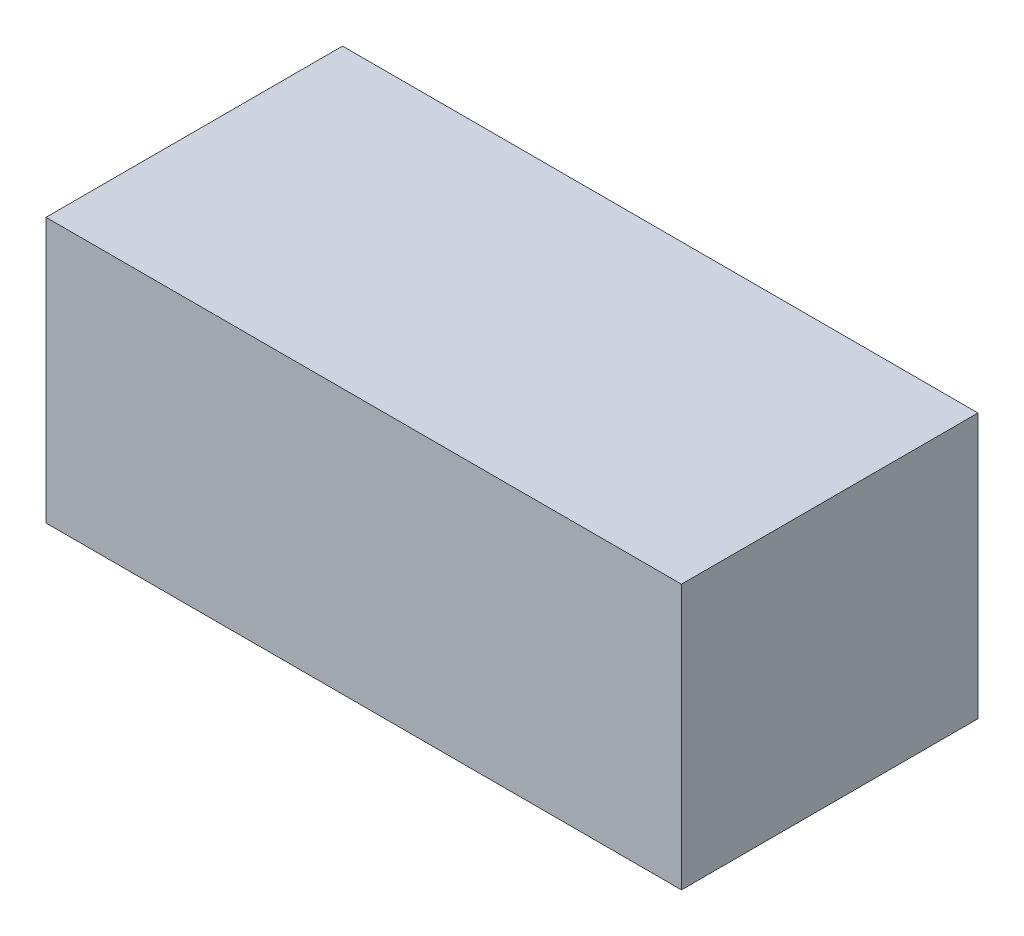
SolidWorks part; units mm, degrees
ref_plane "Front Plane" through (0, 0, 0) normal (0, 0, 1) x (1, 0, 0)
ref_plane "Top Plane" through (0, 0, 0) normal (0, 1, 0) x (1, 0, 0)
ref_plane "Right Plane" through (0, 0, 0) normal (1, 0, 0) x (0, 0, -1)
sketch "Sketch2" plane through (0, 0, 0) normal (0, 1, 0) x (1, 0, 0)
  line L1 (-30, 14) -> (30, 14)
  line L2 (-30, 14) -> (-30, -14)
  line L3 (-30, -14) -> (30, -14)
  line L4 (30, 14) -> (30, -14)
  line L5 (-30, 14) -> (30, -14) construction
  line L6 (-30, -14) -> (30, 14) construction
  point P0 (0, 0)
  dimension "D1" = 28
  dimension "D2" = 60
extrude "Boss-Extrude1" add sketch "Sketch2" along normal blind 25
